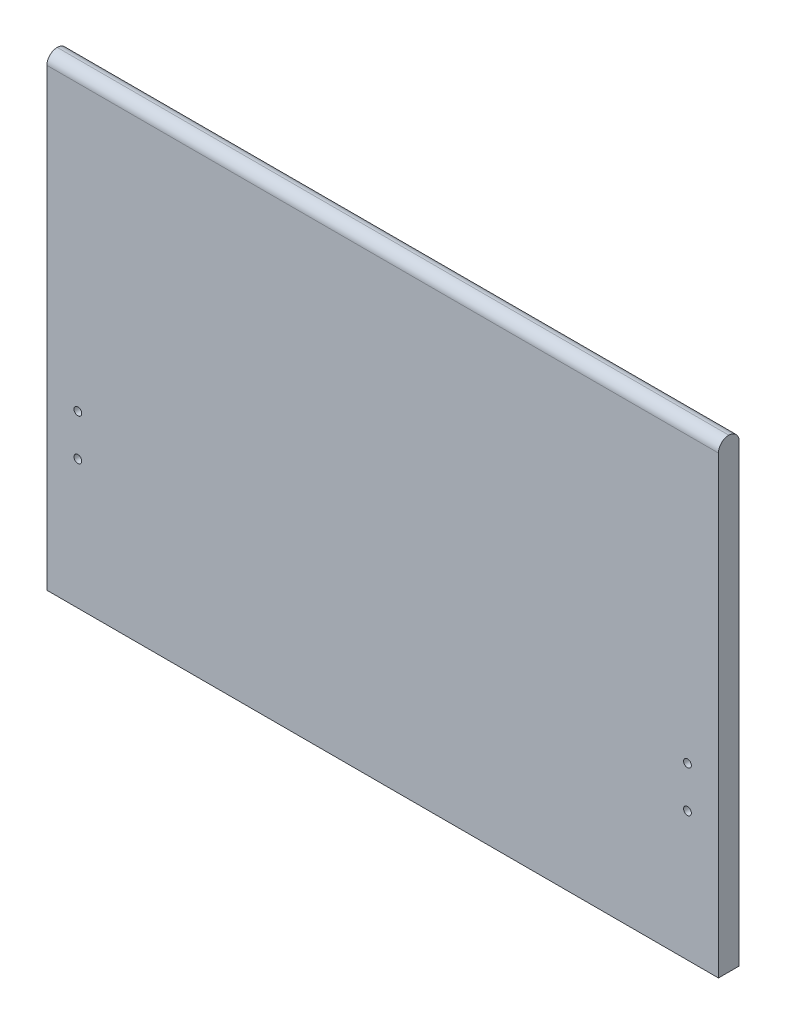
SolidWorks part; units mm, degrees
material "Faggio"
ref_plane "Piano frontale" through (0, 0, 0) normal (0, 0, 1) x (1, 0, 0)
ref_plane "Piano superiore" through (0, 0, 0) normal (0, 1, 0) x (1, 0, 0)
ref_plane "Piano destro" through (0, 0, 0) normal (1, 0, 0) x (0, 0, -1)
sketch "Schizzo1" plane through (0, 0, 0) normal (0, 0, 1) x (1, 0, 0)
  line L1 (0, 0) -> (1300, 0)
  line L2 (0, 0) -> (0, -900)
  line L3 (0, -900) -> (1300, -900)
  line L4 (1300, 0) -> (1300, -900)
  dimension "D1" = 1300
  dimension "D2" = 900
extrude "Estrusione-Estrusione1" add sketch "Schizzo1" along normal blind 40
fillet "Raccordo1" radius 20 2 edges at (650, 0, 0) (650, 0, 40)
sketch "Schizzo2" plane through (0, 0, 40) normal (0, 0, 1) x (1, 0, 0)
  line L0 (0, -900) -> (1300, -900) construction
  line L1 (0, -20) -> (0, -900) construction
  line L2 (1300, -900) -> (1300, -20) construction
  circle A0 centre (60, -650) radius 7.5
  circle A1 centre (60, -570) radius 7.5
  circle A2 centre (1240, -650) radius 7.5
  circle A3 centre (1240, -570) radius 7.5
  dimension "D1" = 15
  dimension "D2" = 15
  dimension "D3" = 15
  dimension "D4" = 15
  dimension "D5" = 80
  dimension "D6" = 80
  dimension "D7" = 250
  dimension "D8" = 250
  dimension "D9" = 60
  dimension "D10" = 60
  dimension "D11" = 60
  dimension "D12" = 60
extrude "Taglio-Estrusione1" cut sketch "Schizzo2" against normal blind 30
